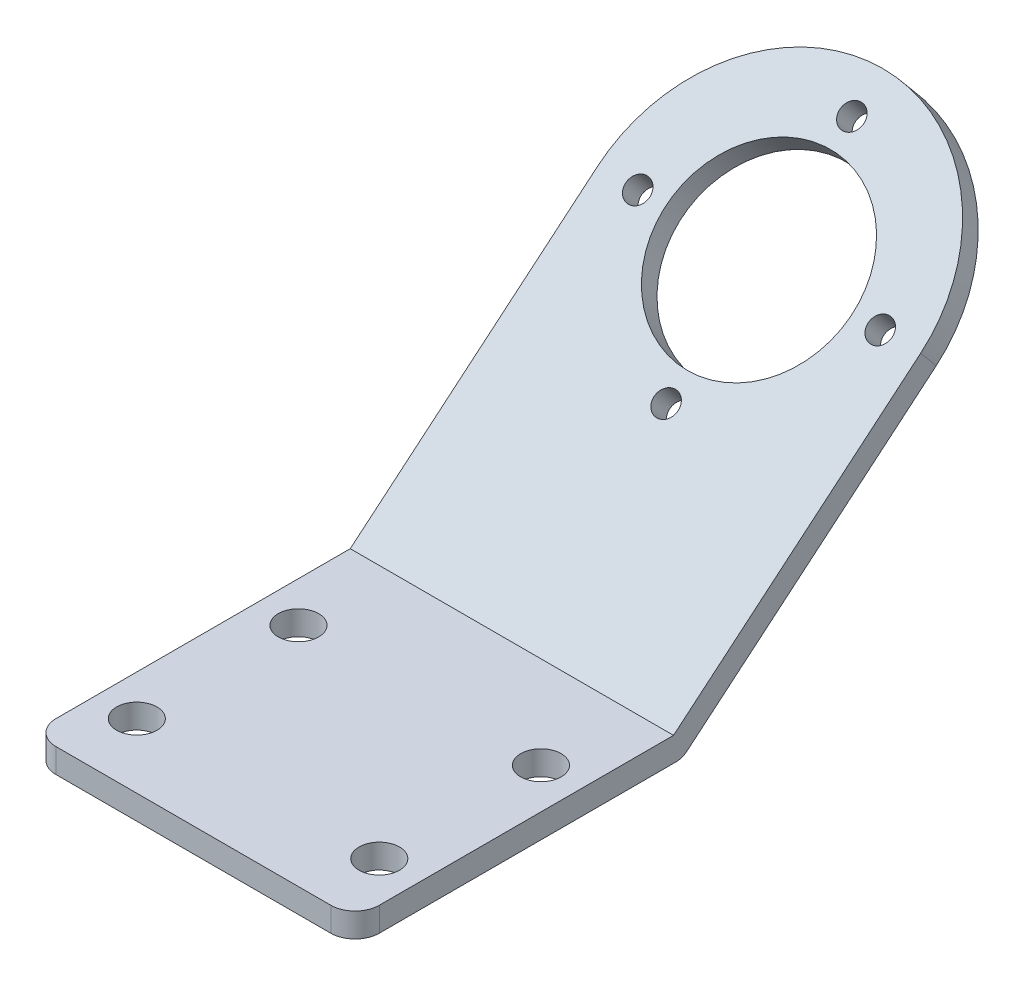
SolidWorks part; units mm, degrees
ref_plane "前视基准面" through (0, 0, 0) normal (0, 0, 1) x (1, 0, 0)
ref_plane "上视基准面" through (0, 0, 0) normal (0, 1, 0) x (1, 0, 0)
ref_plane "右视基准面" through (0, 0, 0) normal (1, 0, 0) x (0, 0, -1)
sketch "草图1" plane through (0, 0, 0) normal (1, 0, 0) x (0, 0, -1)
  line L0 (-39.4081, 0) -> (0, 0)
  line L1 (0, 0) -> (45.8923, 38.5082)
  line L2 (-39.4081, 0) -> (-39.4081, -3)
  line L3 (45.8923, 38.5082) -> (47.8206, 36.21)
  line L4 (-39.4081, -3) -> (0.179, -3)
  line L5 (47.8206, 36.21) -> (1.0919, -3)
  line L6 (1.0919, -3) -> (0.179, -3)
  dimension "D1" = 3
  dimension "D2" = 3
  dimension "D3" = 140
  dimension "D4" = 61
  dimension "D5" = 40.5
  dimension "D6" = 40
extrude "凸台-拉伸1" add sketch "草图1" along normal blind 40
sketch "草图3" plane through (0, 0, 0) normal (0, 1, 0) x (1, 0, 0)
  line L0 (5, -11.4081) -> (35, -11.4081) construction
  line L1 (40, -39.4081) -> (0, -39.4081) construction
  line L2 (35, -11.4081) -> (35, -31.4081) construction
  line L3 (5, -31.4081) -> (35, -31.4081) construction
  line L4 (5, -11.4081) -> (5, -31.4081) construction
  line L5 (0, 0) -> (0, -39.4081) construction
  circle A0 centre (5, -31.4081) radius 2.5
  circle A1 centre (5, -11.4081) radius 2.5
  circle A2 centre (35, -11.4081) radius 2.5
  circle A3 centre (35, -31.4081) radius 2.5
  dimension "D1" = 5
  dimension "D5" = 5
  dimension "D6" = 5
  dimension "D7" = 5
  dimension "D2" = 30
  dimension "D3" = 20
  dimension "D4" = 8
  dimension "D8" = 5
extrude "切除-拉伸1" cut sketch "草图3" against normal blind 40
fillet "圆角1" radius 3 1 edges at (40, -1.5, 39.4081)
fillet "圆角2" radius 3 1 edges at (0, -1.5, 39.4081)
fillet "圆角3" radius 20 1 edges at (0, 37.3591, -46.8564)
fillet "圆角4" radius 20 1 edges at (40, 37.3591, -46.8564)
sketch "草图4" plane through (0, 0, 0) normal (0, 0.766, 0.6428) x (1, 0, 0)
  line L0 (20, 39.9081) -> (20, 56.2214) construction
  line L1 (20, 39.9081) -> (37.3118, 39.9081) construction
  line L2 (20, 39.9081) -> (31.6784, 51.5865) construction
  circle A0 centre (20, 39.9081) radius 11.55
  circle A1 centre (20, 54.9081) radius 1.5
  circle A2 centre (35, 39.9081) radius 1.5
  circle A3 centre (5, 39.9081) radius 1.5
  circle A4 centre (20, 24.9081) radius 1.5
  arc A5 (20, 59.9081) -> (0, 39.9081) centre (20, 39.9081) ccw construction
  dimension "D2" = 23.1
  dimension "D4" = 3
  dimension "D3" = 15
extrude "切除-拉伸2" cut sketch "草图4" against normal blind 40
fillet "圆角5" radius 2 1 edges at (20, -3, -1.0919)
